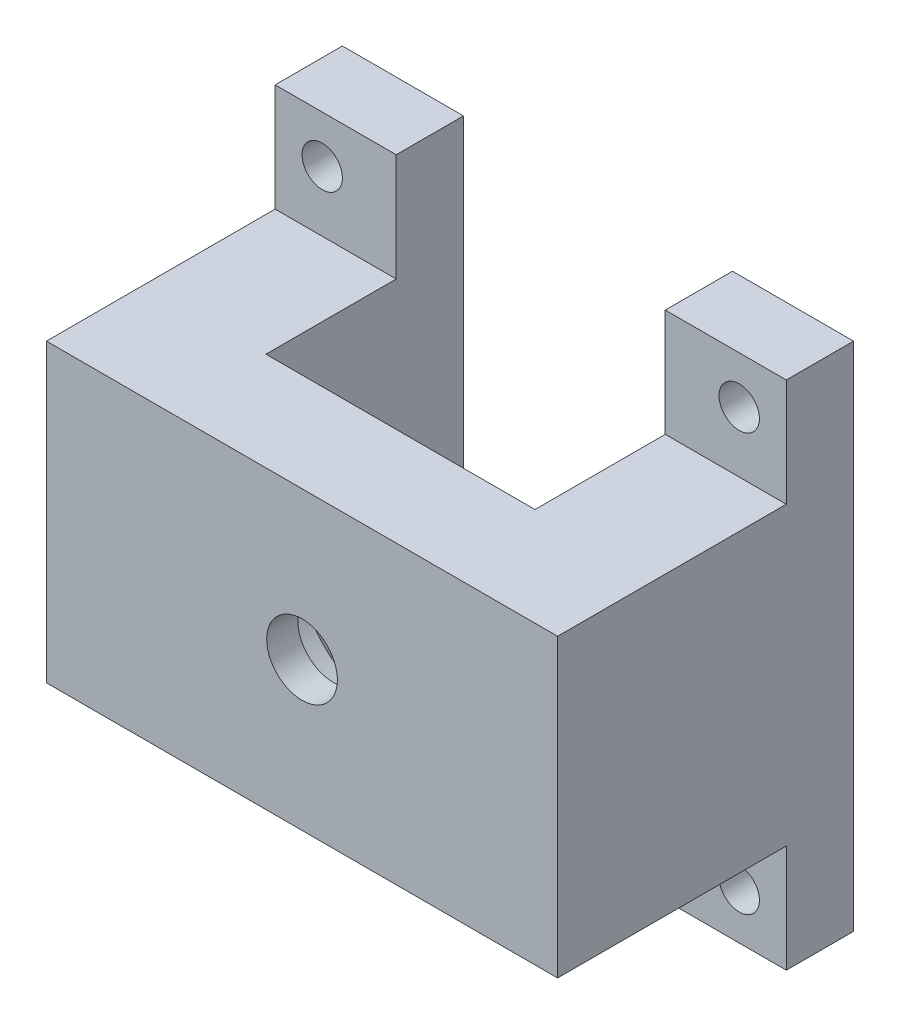
SolidWorks part; units mm, degrees
ref_plane "Front Plane" through (0, 0, 0) normal (0, 0, 1) x (1, 0, 0)
ref_plane "Top Plane" through (0, 0, 0) normal (0, 1, 0) x (1, 0, 0)
ref_plane "Right Plane" through (0, 0, 0) normal (1, 0, 0) x (0, 0, -1)
sketch "Sketch1" plane through (0, 0, 0) normal (0, 0, 1) x (1, 0, 0)
  line L1 (-19, 19) -> (19, 19)
  line L2 (-19, 19) -> (-19, -19)
  line L3 (-19, -19) -> (19, -19)
  line L4 (19, 19) -> (19, -19)
  line L5 (-19, 19) -> (19, -19) construction
  line L6 (-19, -19) -> (19, 19) construction
  point P0 (0, 0)
  dimension "D1" = 38
  dimension "D2" = 38
extrude "Boss-Extrude1" add sketch "Sketch1" along normal blind 22 contours L2 L3 L4 L1
sketch "Sketch2" plane through (0, -19, 0) normal (0, -1, 0) x (1, 0, 0)
  line L0 (-19, 0) -> (19, 0) construction
  line L1 (-10, 0) -> (10, 0)
  line L2 (-10, 0) -> (-10, 14.682)
  line L3 (-10, 14.682) -> (10, 14.682)
  line L4 (10, 0) -> (10, 14.682)
  point P6 (0, 14.682)
  dimension "D1" = 20
  dimension "D2" = 14.682
extrude "Cut-Extrude1" cut sketch "Sketch2" against normal through all
sketch "Sketch3" plane through (0, 0, 14.682) normal (0, 0, -1) x (-1, 0, 0)
  circle A0 centre (0, 0) radius 8
  dimension "D1" = 16
extrude "Cut-Extrude2" cut sketch "Sketch3" against normal blind 5
sketch "Sketch4" plane through (0, 0, 19.682) normal (0, 0, -1) x (-1, 0, 0)
  circle A0 centre (0, 0) radius 2.625
  dimension "D1" = 5.25
extrude "Cut-Extrude3" cut sketch "Sketch4" against normal through all
sketch "Sketch7" plane through (0, 0, 22) normal (0, 0, 1) x (1, 0, 0)
  line L1 (-15.5, -15.5) -> (15.5, -15.5) construction
  line L2 (-15.5, -15.5) -> (-15.5, 15.5) construction
  line L3 (-15.5, 15.5) -> (15.5, 15.5) construction
  line L4 (15.5, -15.5) -> (15.5, 15.5) construction
  line L5 (-15.5, -15.5) -> (15.5, 15.5) construction
  line L6 (-15.5, 15.5) -> (15.5, -15.5) construction
  circle A4 centre (-15.5, 15.5) radius 1.5
  circle A5 centre (15.5, 15.5) radius 1.5
  circle A6 centre (15.5, -15.5) radius 1.5
  circle A7 centre (-15.5, -15.5) radius 1.5
  point P0 (0, 0)
  point P9 (15.4157, 15.4157)
  point P10 (15.5, -15.6583)
  dimension "D1" = 31
  dimension "D4" = 3
  dimension "D2" = 2
  dimension "D3" = 2
extrude "Cut-Extrude6" cut sketch "Sketch7" against normal through all
sketch "Sketch6" plane through (0, 0, 22) normal (0, 0, 1) x (1, 0, 0)
  line L0 (19, 19) -> (19, -19) construction
  line L5 (-19, -19) -> (19, -19)
  line L7 (-19, -19) -> (-19, -11)
  line L8 (-19, -11) -> (19, -11)
  line L17 (19, -19) -> (19, -11)
  line L19 (-19, 19) -> (19, 19)
  line L20 (-19, 19) -> (-19, 11)
  line L21 (-19, 11) -> (19, 11)
  line L22 (19, 19) -> (19, 11)
  dimension "D1" = 8
extrude "Cut-Extrude4" cut sketch "Sketch6" against normal offset from surface (17 mm away) 5 up to face at (17, -15.5, 0)
